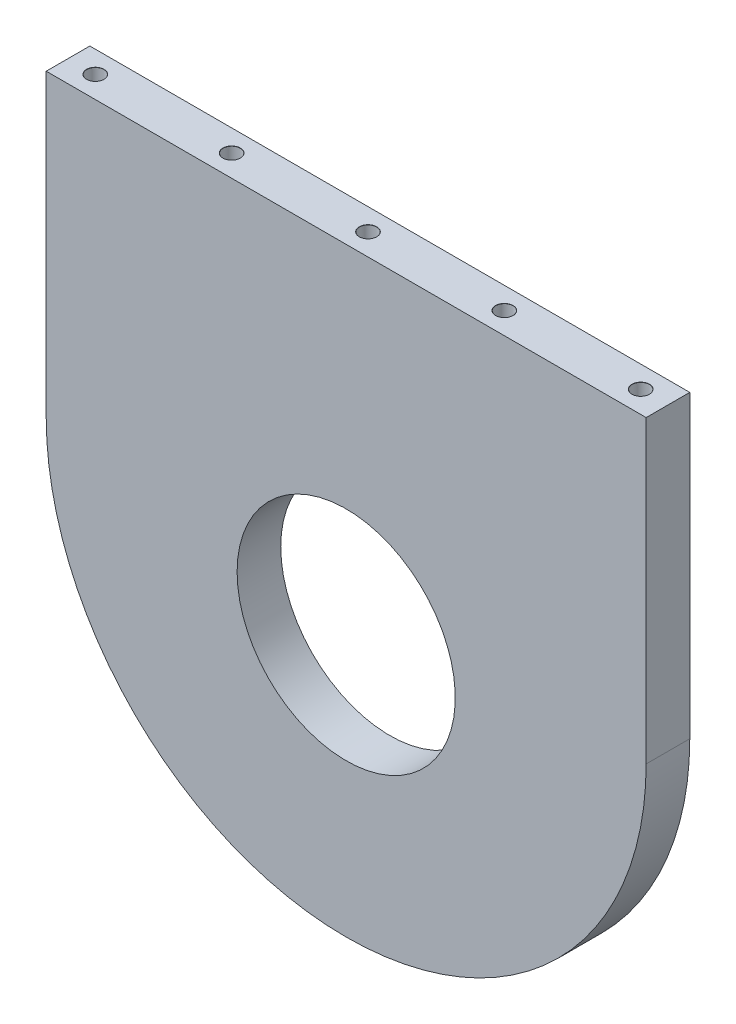
SolidWorks part; units mm, degrees
material "6061-T6 (SS)"
ref_plane "Front Plane" through (0, 0, 0) normal (0, 0, 1) x (1, 0, 0)
ref_plane "Top Plane" through (0, 0, 0) normal (0, 1, 0) x (1, 0, 0)
ref_plane "Right Plane" through (0, 0, 0) normal (1, 0, 0) x (0, 0, -1)
sketch "Sketch1" plane through (0, 0, 0) normal (0, 0, 1) x (1, 0, 0)
  line L1 (0, 0) -> (110, 0)
  line L2 (0, 0) -> (0, 110)
  line L3 (0, 110) -> (110, 110)
  line L4 (110, 0) -> (110, 110)
  dimension "D1" = 110
  dimension "D2" = 110
extrude "Boss-Extrude1" add sketch "Sketch1" along normal blind 8
sketch "Sketch2" plane through (0, 110, 0) normal (0, 1, 0) x (1, 0, 0)
  line L0 (0, -4) -> (110, -4) construction
  line L1 (0, -8) -> (0, 0) construction
  line L2 (110, -8) -> (110, 0) construction
  point P9 (55, -4)
  point P18 (80, -4)
  point P19 (105, -4)
  point P20 (55, -4)
  point P21 (80, -4)
  point P22 (30, -4)
  point P23 (55, -4)
  point P24 (30, -4)
  point P25 (5, -4)
  dimension "D1" = 3
  dimension "D2" = 3
hole_wizard "Tap Drill for M3 Helicoil1" positions "Sketch2" profile "Sketch4" hole size "M3x0.5" standard "DIN"
sketch "Sketch4" plane through (5, 110, 4) normal (1, 0, 0) x (0, 0, 1)
  line L0 (0, 0) -> (0, 6.9464)
  line L1 (0, 6.9464) -> (1.575, 6)
  line L2 (1.575, 6) -> (1.575, 0.025)
  line L3 (1.575, 0.025) -> (1.6, 0)
  line L5 (1.6, 0) -> (0, 0)
  line L6 (-1.575, 0.025) -> (-1.6, 0) construction
  line L10 (0, 6.9464) -> (-1.575, 6) construction
  line L11 (0, -6.35) -> (0, 107.95) construction
  dimension "Hole Dia." = 3.15
  dimension "Hole Depth" = 6
  dimension "Near C'Sink Dia." = 3.2
  dimension "Near C'Sink Angle" = 90
  dimension "Drill Angle" = 118
sketch "Sketch5" plane through (0, 0, 0) normal (0, 0, -1) x (-1, 0, 0)
  circle A0 centre (-55, 48) radius 40 construction
  point P8 (-55, 48)
hole_wizard "Ø40.0 (40) Diameter Hole1" positions "Sketch5" profile "Sketch7" hole size "Ø40.0" standard "DIN" end condition through all
sketch "Sketch7" plane through (55, 48, 0) normal (1, 0, 0) x (0, 1, 0)
  line L0 (0, 0) -> (0, 8)
  line L1 (0, 8) -> (20, 8)
  line L2 (20, 8) -> (20, 0)
  line L5 (20, 0) -> (0, 0)
  line L11 (0, -6.35) -> (0, 107.95) construction
  dimension "Thru Hole Dia." = 40
  dimension "Thru Hole Depth" = 8
fillet "Fillet1" radius 55 2 edges at (110, 0, 4) (0, 0, 4)
